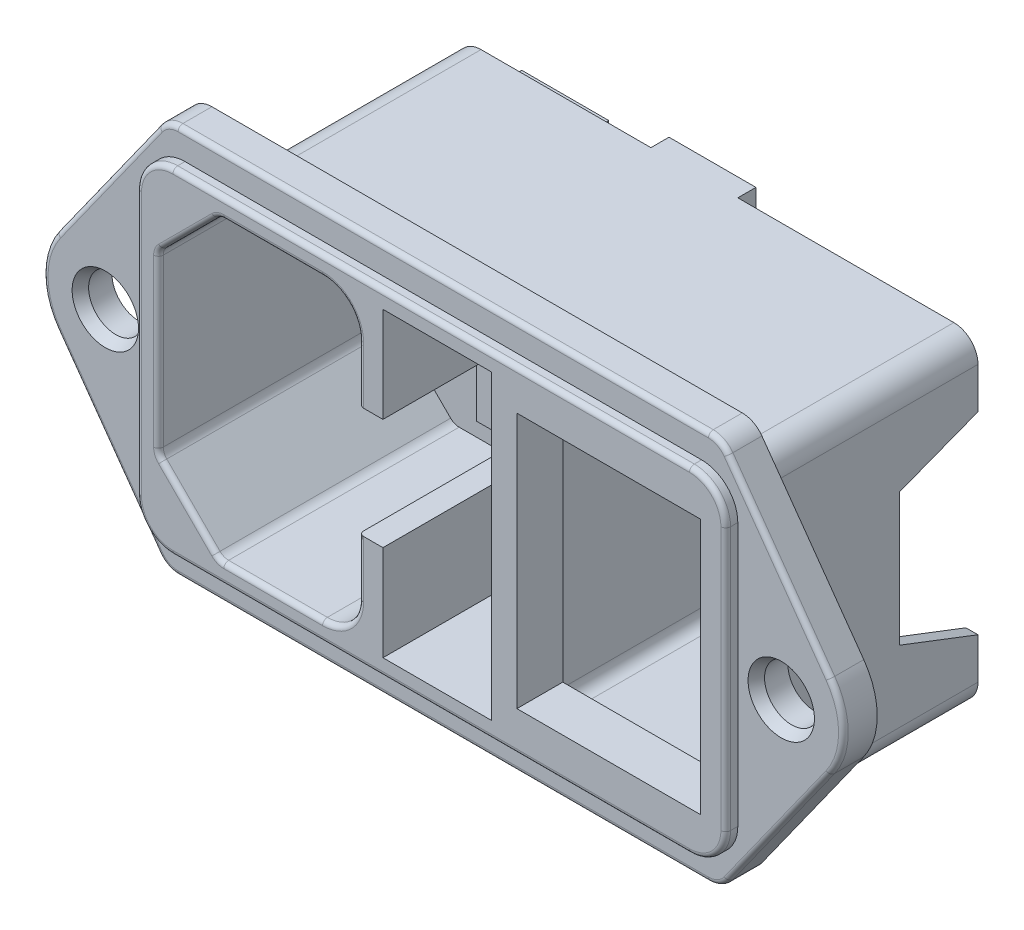
SolidWorks part; units mm, degrees
material "ABS"
ref_plane "Спереди" through (0, 0, 0) normal (0, 0, 1) x (1, 0, 0)
ref_plane "Сверху" through (0, 0, 0) normal (0, 1, 0) x (1, 0, 0)
ref_plane "Справа" through (0, 0, 0) normal (1, 0, 0) x (0, 0, -1)
sketch "Эскиз1" plane through (0, 0, 0) normal (0, 0, 1) x (1, 0, 0)
  line L0 (-23.5982, -15.3114) -> (-32.0346, -3.4843)
  line L1 (-21.97, -16.15) -> (21.97, -16.15)
  line L2 (-23, -16.15) -> (-23, 16.15) construction
  line L3 (-21.97, 16.15) -> (21.97, 16.15)
  line L4 (23, -16.15) -> (23, 16.15) construction
  line L5 (0, 16.15) -> (0, -16.15) construction
  line L6 (-23, 0) -> (23, 0) construction
  line L7 (-32.0346, 3.4843) -> (-23.5982, 15.3114)
  line L8 (-23, 0) -> (-34.52, 0) construction
  line L9 (32.0346, 3.4843) -> (23.5982, 15.3114)
  line L10 (23.5982, -15.3114) -> (32.0346, -3.4843)
  arc A0 (-32.0346, 3.4843) -> (-32.0346, -3.4843) centre (-27.15, 0) ccw
  arc A1 (-21.97, -16.15) -> (-23.5982, -15.3114) centre (-21.97, -14.15) cw
  arc A2 (-21.97, 16.15) -> (-23.5982, 15.3114) centre (-21.97, 14.15) ccw
  arc A3 (21.97, 16.15) -> (23.5982, 15.3114) centre (21.97, 14.15) cw
  arc A4 (21.97, -16.15) -> (23.5982, -15.3114) centre (21.97, -14.15) ccw
  arc A5 (32.0346, 3.4843) -> (32.0346, -3.4843) centre (27.15, 0) cw
  point P0 (0, 0)
  point P17 (-33.15, 0)
  point P22 (0, 0)
  dimension "D3" = 6
  dimension "D4" = 2
  dimension "D5" = 66.3
  dimension "D1" = 46
  dimension "D2" = 32.3
extrude "Корпус_основа" add sketch "Эскиз1" along normal blind 2.8
sketch "Эскиз2" plane through (0, 0, 2.8) normal (0, 0, 1) x (1, 0, 0)
  line L1 (-21.4, -13.9) -> (21.4, -13.9)
  line L2 (-24.4, -10.9) -> (-24.4, 10.9)
  line L3 (-21.4, 13.9) -> (21.4, 13.9)
  line L4 (24.4, -10.9) -> (24.4, 10.9)
  line L5 (0, 13.9) -> (0, -13.9) construction
  line L6 (-24.4, 0) -> (24.4, 0) construction
  arc A0 (24.4, 10.9) -> (21.4, 13.9) centre (21.4, 10.9) ccw
  arc A1 (24.4, -10.9) -> (21.4, -13.9) centre (21.4, -10.9) cw
  arc A2 (-21.4, -13.9) -> (-24.4, -10.9) centre (-21.4, -10.9) cw
  arc A3 (-21.4, 13.9) -> (-24.4, 10.9) centre (-21.4, 10.9) ccw
  point P0 (0, 0)
  dimension "D3" = 3
  dimension "D1" = 27.8
  dimension "D2" = 48.8
extrude "Выступ_спереди" add sketch "Эскиз2" along normal blind 1
sketch "Эскиз4" plane through (0, 0, 0) normal (0, 0, -1) x (-1, 0, 0)
  line L0 (19.0858, 12.8142) -> (22.9142, 8.9858)
  line L1 (-21.5, -13.4) -> (17.6716, -13.4)
  line L2 (-23.5, -11.4) -> (-23.5, 11.4)
  line L3 (-21.5, 13.4) -> (17.6716, 13.4)
  line L4 (23.5, -7.5716) -> (23.5, 7.5716)
  line L5 (0, 13.4) -> (0, -13.4) construction
  line L6 (-23.5, 0) -> (23.5, 0) construction
  line L7 (19.0858, -12.8142) -> (22.9142, -8.9858)
  arc A0 (19.0858, 12.8142) -> (17.6716, 13.4) centre (17.6716, 11.4) ccw
  arc A1 (23.5, 7.5716) -> (22.9142, 8.9858) centre (21.5, 7.5716) ccw
  arc A2 (23.5, -7.5716) -> (22.9142, -8.9858) centre (21.5, -7.5716) cw
  arc A3 (19.0858, -12.8142) -> (17.6716, -13.4) centre (17.6716, -11.4) cw
  arc A4 (-21.5, -13.4) -> (-23.5, -11.4) centre (-21.5, -11.4) cw
  arc A5 (-21.5, 13.4) -> (-23.5, 11.4) centre (-21.5, 11.4) ccw
  point P0 (0, 0)
  point P1 (23.5, 13.4)
  point P9 (0, 0)
  point P16 (18.5, 13.4)
  point P19 (23.5, 8.4)
  point P22 (23.5, -8.4)
  point P25 (18.5, -13.4)
  point P104 (23.5, -13.4)
  dimension "D3" = 2
  dimension "D1" = 47
  dimension "D2" = 26.8
extrude "Корпус_продолжение" add sketch "Эскиз4" along normal blind 18
sketch "Эскиз3" plane through (0, 0, 3.8) normal (0, 0, 1) x (1, 0, 0)
  line L0 (-24.4, 10.9) -> (-24.4, -10.9) construction
  line L1 (-17.1858, -12.3) -> (-9, -12.3)
  line L2 (-22.6, -6.8858) -> (-22.6, 6.8858)
  line L3 (-17.1858, 12.3) -> (-9, 12.3)
  line L4 (-6, -9.3) -> (-6, -4.6)
  line L5 (-4, -4.6) -> (-6, -4.6)
  line L6 (5, -12.5) -> (-4, -12.5)
  line L7 (0, 0) -> (0.5, 0) construction
  line L8 (-22.3071, 7.5929) -> (-17.8929, 12.0071)
  line L9 (-22.3071, -7.5929) -> (-17.8929, -12.0071)
  line L10 (5, -12.5) -> (5, 12.5)
  line L11 (5, 12.5) -> (-4, 12.5)
  line L12 (-4, -12.5) -> (-4, -4.6)
  line L13 (0.5, 12.5) -> (0.5, -12.5) construction
  line L14 (5, 0) -> (0.5, 0) construction
  line L15 (-4, 4.6) -> (-6, 4.6)
  line L16 (-4, 4.6) -> (-4, 12.5)
  line L17 (-6, 4.6) -> (-6, 9.3)
  arc A0 (-6, -9.3) -> (-9, -12.3) centre (-9, -9.3) cw
  arc A1 (-6, 9.3) -> (-9, 12.3) centre (-9, 9.3) ccw
  arc A2 (-17.8929, -12.0071) -> (-17.1858, -12.3) centre (-17.1858, -11.3) ccw
  arc A3 (-22.6, -6.8858) -> (-22.3071, -7.5929) centre (-21.6, -6.8858) ccw
  arc A4 (-22.6, 6.8858) -> (-22.3071, 7.5929) centre (-21.6, 6.8858) cw
  arc A5 (-17.1858, 12.3) -> (-17.8929, 12.0071) centre (-17.1858, 11.3) ccw
  point P2 (-22.6, -12.3)
  point P3 (-22.6, 12.3)
  point P23 (-17.6, -12.3)
  point P26 (-22.6, -7.3)
  point P29 (-22.6, 7.3)
  point P32 (-17.6, 12.3)
  point P33 (0.5, 0)
  dimension "D4" = 3
  dimension "D5" = 1
  dimension "D1" = 1.8
  dimension "D2" = 24.6
  dimension "D3" = 16.6
  dimension "D6" = 25
  dimension "D7" = 9
  dimension "D10" = 2
  dimension "D11" = 9.2
extrude "Вырез_вилка_и_предохранитель" cut sketch "Эскиз3" against normal blind 19.5
sketch "Эскиз5" plane through (0, 0, -18) normal (0, 0, -1) x (-1, 0, 0)
  line L0 (-23.5, 11.4) -> (-23.5, -11.4) construction
  line L1 (-21.5, -12.2) -> (-7.9, -12.2)
  line L2 (-22.5, -11.2) -> (-22.5, 11.2)
  line L3 (-21.5, 12.2) -> (-7.9, 12.2)
  line L4 (-6.9, -11.2) -> (-6.9, 11.2)
  line L5 (-14.7, 12.2) -> (-14.7, -12.2) construction
  line L6 (-22.5, 0) -> (-6.9, 0) construction
  line L7 (-6.9, 0) -> (0, 0) construction
  arc A0 (-6.9, -11.2) -> (-7.9, -12.2) centre (-7.9, -11.2) cw
  arc A1 (-6.9, 11.2) -> (-7.9, 12.2) centre (-7.9, 11.2) ccw
  arc A2 (-21.5, 12.2) -> (-22.5, 11.2) centre (-21.5, 11.2) ccw
  arc A3 (-22.5, -11.2) -> (-21.5, -12.2) centre (-21.5, -11.2) ccw
  point P0 (-14.7, 0)
  dimension "D4" = 1
  dimension "D1" = 1
  dimension "D2" = 24.4
  dimension "D3" = 15.6
extrude "Вырез_под_выключатель" cut sketch "Эскиз5" against normal up to surface (18 mm away) up to plane "Спереди"
sketch "Эскиз6" plane through (23.5, 0, 0) normal (1, 0, 0) x (0, 0, -1)
  line L0 (18, -8) -> (11.5, -5.5)
  line L1 (18, 11.4) -> (18, -11.4) construction
  line L2 (11.5, -5.5) -> (11.5, 5.5)
  line L3 (11.5, 0) -> (18, 0) construction
  line L4 (18, 8) -> (11.5, 5.5)
  line L5 (18, 8) -> (18, -8)
  dimension "D1" = 16
  dimension "D2" = 6.5
  dimension "D3" = 5.5
extrude "Боковой_вырез_под_выключатель" cut sketch "Эскиз6" against normal up to next
sketch "Эскиз7" plane through (0, 0, 3.8) normal (0, 0, 1) x (1, 0, 0)
  line L0 (0, 0) -> (7.1, 0) construction
  line L1 (7.1, -10.6) -> (22.3, -10.6)
  line L2 (7.1, -10.6) -> (7.1, 10.6)
  line L3 (7.1, 10.6) -> (22.3, 10.6)
  line L4 (22.3, -10.6) -> (22.3, 10.6)
  line L5 (14.7, 10.6) -> (14.7, -10.6) construction
  line L6 (7.1, 0) -> (22.3, 0) construction
  line L8 (14.7, 12.2) -> (14.7, -12.2) construction
  point P0 (14.7, 0)
  dimension "D1" = 15.2
  dimension "D2" = 21.2
extrude "Вырез_под_выключатель_спереди" cut sketch "Эскиз7" against normal up to next
ref_axis "Ось_монтажа_выключателя" through (14.7, 0, -18) along (0, 0, 1)
sketch "Эскиз8" plane through (0, 0, -15.7) normal (0, 0, 1) x (1, 0, 0)
  line L0 (0, 0) -> (-15.6, 0) construction
  line L1 (-12.6, 8) -> (-10.6, 8)
  line L2 (-14.35, 4.25) -> (-8.85, 4.25)
  line L3 (-14.35, 4.25) -> (-14.35, 9.75)
  line L4 (-14.35, 9.75) -> (-8.85, 9.75)
  line L5 (-8.85, 4.25) -> (-8.85, 9.75)
  line L6 (-11.6, 9.75) -> (-11.6, 4.25) construction
  line L7 (-14.35, 7) -> (-8.85, 7) construction
  line L8 (-10.6, 6) -> (-10.6, 8)
  line L9 (-12.6, 6) -> (-10.6, 6)
  line L10 (-12.6, 6) -> (-12.6, 8)
  line L11 (-16.6, 1) -> (-14.6, 1)
  line L12 (-18.35, -2.75) -> (-12.85, -2.75)
  line L13 (-18.35, -2.75) -> (-18.35, 2.75)
  line L14 (-18.35, 2.75) -> (-12.85, 2.75)
  line L15 (-12.85, -2.75) -> (-12.85, 2.75)
  line L16 (-15.6, 2.75) -> (-15.6, -2.75) construction
  line L17 (-18.35, 0) -> (-12.85, 0) construction
  line L18 (-14.6, -1) -> (-14.6, 1)
  line L19 (-16.6, -1) -> (-14.6, -1)
  line L20 (-16.6, -1) -> (-16.6, 1)
  line L21 (-12.6, -8) -> (-12.6, -6)
  line L22 (-14.35, -9.75) -> (-8.85, -9.75)
  line L23 (-14.35, -9.75) -> (-14.35, -4.25)
  line L24 (-14.35, -4.25) -> (-8.85, -4.25)
  line L25 (-8.85, -9.75) -> (-8.85, -4.25)
  line L26 (-11.6, -4.25) -> (-11.6, -9.75) construction
  line L27 (-14.35, -7) -> (-8.85, -7) construction
  line L28 (-12.6, -6) -> (-10.6, -6)
  line L29 (-10.6, -8) -> (-10.6, -6)
  line L30 (-12.6, -8) -> (-10.6, -8)
  line L31 (-22.6, 6.8858) -> (-22.6, -6.8858) construction
  point P0 (-11.6, 7)
  point P6 (-15.6, 0)
  point P8 (-11.6, -7)
  point P9 (-11.6, 7)
  point P21 (-11.6, -7)
  dimension "D1" = 4
  dimension "D2" = 7
  dimension "D3" = 5.5
  dimension "D7" = 7
  dimension "D4" = 1.75
  dimension "D5" = 1.75
  dimension "D6" = 1.75
extrude "Бобышка-Вытянуть4" add sketch "Эскиз8" along normal blind 1.4
extrude "Вырез-Вытянуть5" cut sketch "Эскиз8<2>" against normal up to next contours L10 L9 L8 L1 | L20 L19 L18 L11 | L21 L30 L29 L28 region at (-11.6, 7, -15.7) region at (-15.6, 0, -15.7) region at (-11.6, -7, -15.7)
sketch "Эскиз8<2>" plane through (0, 0, -15.7) normal (0, 0, 1) x (1, 0, 0) same geometry as "Эскиз8"
hole_wizard "Зенковка для винта с полупотайной головкой M41" positions "Эскиз10" profile "Эскиз11" countersink size "M4" standard "ISO" end condition up to next
sketch "Эскиз10" plane through (0, 0, 2.8) normal (0, 0, 1) x (1, 0, 0)
  line L0 (0, 0) -> (-28, 0) construction
  line L2 (0, 0) -> (28, 0) construction
  point P0 (-28, 0)
  point P2 (28, 0)
  dimension "D1" = 56
sketch "Эскиз11" plane through (-28, 0, 2.8) normal (1, 0, 0) x (0, -1, 0)
  line L0 (0, 0) -> (0, 2.8)
  line L1 (0, 2.8) -> (2.25, 2.8)
  line L2 (2.25, 2.8) -> (2.25, 0.866)
  line L3 (2.25, 0.866) -> (2.75, 0)
  line L5 (2.75, 0) -> (0, 0)
  line L6 (-2.25, 0.866) -> (-2.75, 0) construction
  line L11 (0, -6.35) -> (0, 107.95) construction
  dimension "Диаметр сквозного отверстия" = 4.5
  dimension "Глубина сквозного отверстия" = 2.8
  dimension "Диаметр передней зенковки" = 5.5
  dimension "Угол передней зенковки" = 60
sketch "Эскиз13" plane through (0, 0, -18) normal (0, 0, -1) x (-1, 0, 0)
  line L0 (8.6, 10.3) -> (12.8, 10.3)
  line L1 (8.6, 1.9) -> (11.4, 1.9)
  line L2 (8.6, 1.9) -> (8.6, 12.1) construction
  line L3 (8.6, 12.1) -> (15.8, 12.1)
  line L4 (15.8, 5.1) -> (15.8, 12.1)
  line L5 (11.6, 12.1) -> (11.6, 1.9) construction
  line L6 (8.6, 7) -> (15.8, 7) construction
  line L7 (14.4, 5.3) -> (14.4, 8.7)
  line L8 (8.6, 3.7) -> (12.8, 3.7)
  line L10 (11.4, 1.9) -> (11.4, 0)
  line L11 (12.8, 10.3) -> (14.4, 8.7)
  line L12 (0, 0) -> (15.6, 0) construction
  line L13 (12.8, 3.7) -> (14.4, 5.3)
  line L14 (8.6, 10.3) -> (8.6, 12.1)
  line L15 (8.6, 1.9) -> (8.6, 3.7)
  line L16 (14.4, 3.3) -> (18.6, 3.3)
  line L17 (18.6, 3.3) -> (18.6, 5.1)
  line L18 (18.6, 5.1) -> (15.8, 5.1)
  line L19 (0, 0) -> (4.8044, 0) construction
  line L20 (12.8, 1.7) -> (12.8, 0)
  line L21 (14.4, 3.3) -> (12.8, 1.7)
  line L22 (15.6, 2.75) -> (15.6, -2.75) construction
  line L23 (11.4, 0) -> (12.8, 0)
  point P0 (11.6, 7)
  point P5 (12.8, 3.3)
  point P48 (15.8, 1.9)
  dimension "D1" = 10.2
  dimension "D2" = 7.2
  dimension "D4" = 1.6
  dimension "D5" = 1.6
  dimension "D3" = 1.8
  dimension "D6" = 1.4
  dimension "D7" = 3
  dimension "D8" = 1.4
  dimension "D9" = 7.2
  dimension "D10" = 10.2
  dimension "D11" = 1.8
  dimension "D12" = 3
  dimension "D13" = 1.6
extrude "Бобышка-Вытянуть6" add sketch "Эскиз13" along normal blind 1.5
sketch "Эскиз15" plane through (0, 0, -18) normal (0, 0, -1) x (-1, 0, 0)
  line L0 (17.6716, 13.4) -> (-21.5, 13.4) construction
  line L1 (-3.6, 2.9) -> (3.6, 2.9)
  line L2 (-3.6, 2.9) -> (-3.6, 4.9)
  line L3 (-3.6, 13.4) -> (3.6, 13.4)
  line L4 (3.6, 2.9) -> (3.6, 13.4)
  line L5 (0, 13.4) -> (0, 2.9) construction
  line L6 (0, 8.15) -> (3.6, 8.15) construction
  line L7 (-3.6, 11.4) -> (0.7, 11.4)
  line L8 (2.2, 9.9) -> (2.2, 6.4)
  line L9 (0.7, 4.9) -> (-3.6, 4.9)
  line L10 (-3.6, 11.4) -> (-3.6, 13.4)
  line L11 (8.6, 12.1) -> (8.6, 10.3) construction
  line L12 (0.7, 11.4) -> (2.2, 9.9)
  line L13 (2.2, 6.4) -> (0.7, 4.9)
  point P0 (0, 8.15)
  point P7 (2.2, 11.4)
  point P8 (2.2, 4.9)
  dimension "D1" = 10.5
  dimension "D2" = 7.2
  dimension "D3" = 2
  dimension "D4" = 1.4
  dimension "D5" = 5
  dimension "D6" = 2
extrude "Бобышка-Вытянуть7" add sketch "Эскиз15" along normal blind 1.5
fillet "Скругление2" radius 0.8 4 edges at (-18.6, 3.3, -18.75) (-18.6, 5.1, -18.75) (-8.6, 1.9, -18.75) (-8.6, 3.7, -18.75)
mirror "Зеркальное отражение2" about plane through (0, 0, 0) normal (0, 1, 0) of "Скругление2", "Бобышка-Вытянуть6"
sketch "Эскиз16" plane through (0, 0, -19.5) normal (0, 0, -1) x (-1, 0, 0)
  line L0 (14.4, 7) -> (15.8, 7)
  line L1 (14.4, 8.7) -> (14.4, 5.3) construction
  line L2 (15.8, 5.1) -> (15.8, 12.1) construction
  line L3 (15.8, 7) -> (15.8, 3.3)
  line L4 (14.4, 3.3) -> (17.8, 3.3) construction
  line L5 (15.8, 3.3) -> (14.4, 3.3)
  line L6 (14.4, 3.3) -> (12.8, 1.7)
  line L7 (12.8, 1.7) -> (12.8, -1.7)
  line L8 (12.8, -1.7) -> (14.4, -3.3)
  line L9 (14.4, -3.3) -> (15.8, -3.3)
  line L10 (14.4, -3.3) -> (17.8, -3.3) construction
  line L11 (15.8, -3.3) -> (15.8, -7)
  line L12 (15.8, -5.1) -> (15.8, -12.1) construction
  line L13 (15.8, -7) -> (14.4, -7)
  line L14 (14.4, -8.7) -> (14.4, -5.3) construction
  line L15 (14.4, -7) -> (14.4, -5.3)
  line L16 (14.4, -5.3) -> (12.8, -3.7)
  line L17 (12.8, -3.7) -> (11.4, -3.7)
  line L18 (12.8, -3.7) -> (9.4, -3.7) construction
  line L19 (11.4, -3.7) -> (11.4, -1.9)
  line L20 (11.4, -1.9) -> (11.4, 1.9)
  line L21 (11.4, 1.9) -> (11.4, 3.7)
  line L22 (12.8, 3.7) -> (9.4, 3.7) construction
  line L23 (11.4, 3.7) -> (12.8, 3.7)
  line L24 (12.8, 3.7) -> (14.4, 5.3)
  line L25 (14.4, 5.3) -> (14.4, 7)
extrude "Бобышка-Вытянуть8" add sketch "Эскиз16" along normal blind 1
sketch "Эскиз14" plane through (0, 0, -15.7) normal (0, 0, 1) x (1, 0, 0)
  line L0 (0, 0) -> (0.5, 0) construction
  line L1 (-0.5, 9) -> (1.5, 9)
  line L2 (-0.5, 9) -> (-0.5, 7)
  line L3 (-0.5, 7) -> (1.5, 7)
  line L4 (1.5, 9) -> (1.5, 7)
  line L5 (0.5, 7) -> (0.5, 9) construction
  line L6 (-0.5, 8) -> (1.5, 8) construction
  line L7 (0.5, 0) -> (0.5, 7) construction
  line L8 (-0.5, -7) -> (1.5, -7)
  line L9 (1.5, -9) -> (1.5, -7)
  line L10 (-0.5, -9) -> (1.5, -9)
  line L11 (-0.5, -9) -> (-0.5, -7)
  line L12 (-0.5, 8) -> (-4, 8) construction
  line L13 (-4, 12.5) -> (-4, 4.6) construction
  line L14 (1.5, 8) -> (5, 8) construction
  line L15 (5, -12.5) -> (5, 12.5) construction
  circle A0 centre (0.5, 0) radius 2.5
  point P0 (0.5, 8)
  dimension "D3" = 5
  dimension "D1" = 2
  dimension "D2" = 8
extrude "Вырез-Вытянуть6" cut sketch "Эскиз14" against normal up to next
fillet "Скругление3" radius 0.4 33 edges at (-6, 6.95, 3.8) (-6.8787, 11.4213, 3.8) (-13.0929, 12.3, 3.8) (-17.5685, 12.2239, 3.8) (-20.1, 9.8, 3.8) (-22.5239, 7.2685, 3.8) (-6, -6.95, 3.8) (-6.8787, -11.4213, 3.8) (-13.0929, -12.3, 3.8) (-17.5685, -12.2239, 3.8) (-20.1, -9.8, 3.8) (-22.5239, -7.2685, 3.8) (-33.15, 0, 2.8) (-27.8164, 9.3979, 2.8) (-22.8857, 15.928, 2.8) (0, 16.15, 2.8) (22.8857, 15.928, 2.8) (27.8164, 9.3979, 2.8) (33.15, 0, 2.8) (27.8164, -9.3979, 2.8) (22.8857, -15.928, 2.8) (0, -16.15, 2.8) (-22.8857, -15.928, 2.8) (23.5213, 13.0213, 3.8) (24.4, 0, 3.8) (23.5213, -13.0213, 3.8) (0, -13.9, 3.8) (-23.5213, -13.0213, 3.8) (-24.4, 0, 3.8) (-23.5213, 13.0213, 3.8) (-22.6, 0, 3.8) (-27.8164, -9.3979, 2.8) (0, 13.9, 3.8)
